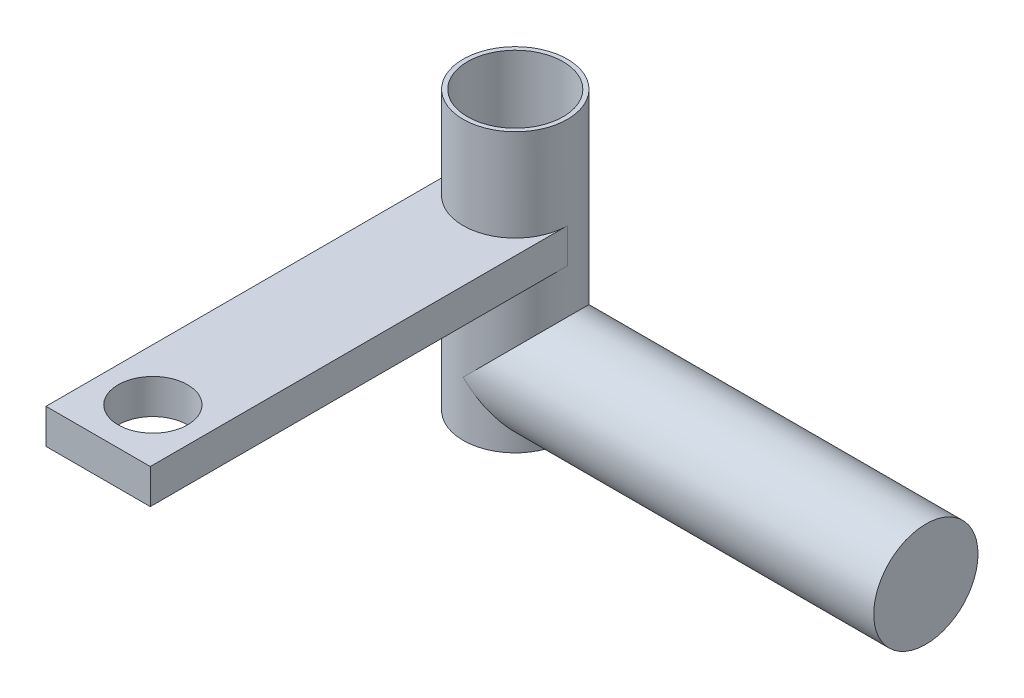
SolidWorks part; units mm, degrees
ref_plane "Front Plane" through (0, 0, 0) normal (0, 0, 1) x (1, 0, 0)
ref_plane "Top Plane" through (0, 0, 0) normal (0, 1, 0) x (1, 0, 0)
ref_plane "Right Plane" through (0, 0, 0) normal (1, 0, 0) x (0, 0, -1)
sketch "Sketch1" plane through (0, 0, 0) normal (0, 1, 0) x (1, 0, 0)
  circle A0 centre (0, 0) radius 9.525
  dimension "D1" = 19.05
extrude "Sleeve" add sketch "Sketch1" along normal blind 50.8
sketch "Sketch2" plane through (0, 0, 0) normal (0, 0, 1) x (1, 0, 0)
  line L0 (0, -10.4775) -> (0, 10.4775) construction
  line L1 (9.525, 33.975) -> (-9.525, 33.975)
  line L2 (9.525, 33.975) -> (9.525, 27.625)
  line L3 (9.525, 27.625) -> (-9.525, 27.625)
  line L4 (-9.525, 33.975) -> (-9.525, 27.625)
  line L5 (9.525, 33.975) -> (-9.525, 27.625) construction
  line L6 (9.525, 27.625) -> (-9.525, 33.975) construction
  point P0 (0, 30.8)
  dimension "D1" = 6.35
  dimension "D2" = 19.05
  dimension "D3" = 30.8
extrude "Bracket" add sketch "Sketch2" along normal blind 76.2
sketch "Sketch4" plane through (0, 0, 0) normal (0, 1, 0) x (1, 0, 0)
  line L0 (0, -27.94) -> (0, 27.94) construction
  circle A0 centre (0, -66.2) radius 6.35
  point P2 (0, 0)
  dimension "D1" = 12.7
  dimension "D2" = 66.2
extrude "Bracket Hole" cut sketch "Sketch4" along normal through all
sketch "Sketch5" plane through (0, 0, 0) normal (1, 0, 0) x (0, 0, -1)
  line L0 (0, 10.4775) -> (0, -10.4775) construction
  circle A0 centre (0, 10) radius 9.525
  dimension "D2" = 19.05
  dimension "D1" = 10
extrude "Shaft" add sketch "Sketch5" along normal blind 75
sketch "Sketch6" plane through (0, 0, 0) normal (0, 1, 0) x (1, 0, 0)
  circle A0 centre (0, 0) radius 8.7313
  dimension "D1" = 17.4625
extrude "Sleeve Hole" cut sketch "Sketch6" along normal through all
equation "\"shaftDiameter\" = 25.4 / 4 * 3mm"
equation "\"shaftLength\"= 75mm"
equation "\"sleeveDiameter\" = 25.4 / 4 * 3mm"
equation "\"sleeveLength\" = 2 * 25.4mm"
equation "\"bracketLength\" = 3 * 25.4mm"
equation "\"D1@Sketch1\"=\"sleeveDiameter\""
equation "\"D1@Sleeve\"=\"sleeveLength\""
equation "\"D3@Sketch2\"=\"sleeveLength\"-20"
equation "\"D1@Bracket\"=\"bracketLength\""
equation "\"tieBarHoleDiameter\"= 25.4 / 2mm"
equation "\"D1@Sketch4\"=\"tieBarHoleDiameter\""
equation "\"D2@Sketch4\"=\"bracketLength\"-10"
equation "\"D2@Sketch5\"=\"shaftDiameter\""
equation "\"D1@Shaft\"=\"shaftLength\""
equation "\"sleeveWallThickness\"= 25.4 / 16"
equation "\"D1@Sketch6\"=\"sleeveDiameter\"-\"sleeveWallThickness\""
